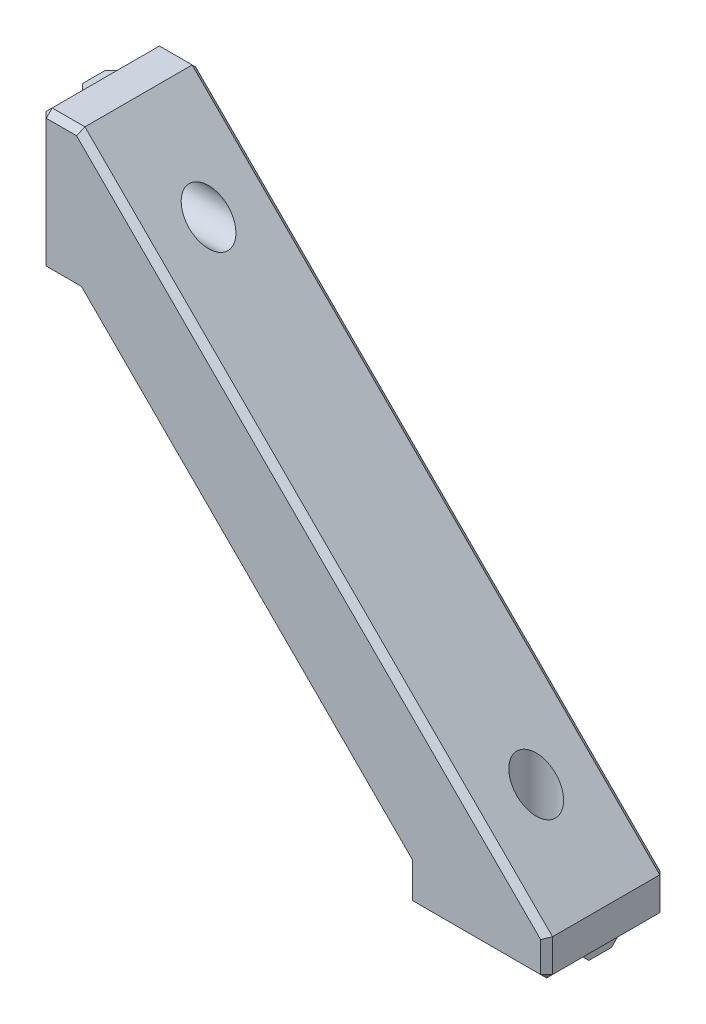
SolidWorks part; units mm, degrees
ref_plane "Front Plane" through (0, 0, 0) normal (0, 0, 1) x (1, 0, 0)
ref_plane "Top Plane" through (0, 0, 0) normal (0, 1, 0) x (1, 0, 0)
ref_plane "Right Plane" through (0, 0, 0) normal (1, 0, 0) x (0, 0, -1)
sketch "Sketch2" plane through (0, 0, 0) normal (0, 0, 1) x (1, 0, 0)
  line L0 (-8.1595, 72.9162) -> (70.3405, -5.5838)
  line L1 (70.3405, -5.5838) -> (46.8405, -5.5838)
  line L2 (46.8405, -5.5838) -> (-8.1595, 49.4162)
  line L3 (-8.1595, 49.4162) -> (-8.1595, 72.9162)
  line L4 (46.8405, -5.5838) -> (-8.1595, -5.5838) construction
  line L5 (-8.1595, -5.5838) -> (-8.1595, 49.4162) construction
  dimension "D1" = 23.5
  dimension "D2" = 55
extrude "Boss-Extrude1" add sketch "Sketch2" along normal mid plane 20
sketch "Sketch29" plane through (-8.1595, 0, 0) normal (-1, 0, 0) x (0, 0, 1)
  line L4 (-10, 72.9162) -> (-10, 49.4162)
  line L5 (-10, 49.4162) -> (10, 49.4162)
  line L6 (10, 49.4162) -> (10, 72.9162)
  line L7 (10, 72.9162) -> (-10, 72.9162)
  line L8 (-10, 72.9162) -> (-10, 49.4162)
  line L9 (-10, 49.4162) -> (10, 49.4162)
  line L10 (10, 49.4162) -> (10, 72.9162)
  line L11 (10, 72.9162) -> (-10, 72.9162)
  dimension "D1" = 0
extrude "Boss-Extrude4" add sketch "Sketch29" along normal blind 6.5
sketch "Sketch30" plane through (0, -5.5838, 0) normal (0, -1, 0) x (1, 0, 0)
  line L4 (46.8405, -10) -> (70.3405, -10)
  line L5 (70.3405, -10) -> (70.3405, 10)
  line L6 (70.3405, 10) -> (46.8405, 10)
  line L7 (46.8405, 10) -> (46.8405, -10)
  line L8 (46.8405, -10) -> (70.3405, -10)
  line L9 (70.3405, -10) -> (70.3405, 10)
  line L10 (70.3405, 10) -> (46.8405, 10)
  line L11 (46.8405, 10) -> (46.8405, -10)
  dimension "D1" = 0
extrude "Boss-Extrude5" add sketch "Sketch30" along normal blind 6.5
chamfer "Chamfer1" distance 1 angle 45 20 edges at (31.0905, 33.6662, -10) (19.3405, 21.9162, -10) (19.3405, 21.9162, 10) (31.0905, 33.6662, 10) (70.3405, -8.8338, 10) (58.5905, -12.0838, 10) (46.8405, -8.8338, 10) (-11.4095, 49.4162, 10) (-14.6595, 61.1662, 10) (-11.4095, 72.9162, 10) (46.8405, -8.8338, -10) (-11.4095, 49.4162, -10) (-14.6595, 49.4162, 0) (-14.6595, 61.1662, -10) (-14.6595, 72.9162, 0) (-11.4095, 72.9162, -10) (70.3405, -8.8338, -10) (70.3405, -12.0838, 0) (58.5905, -12.0838, -10) (46.8405, -12.0838, 0)
sketch "Sketch4" plane through (0, -12.0838, 0) normal (0, -1, 0) x (1, 0, 0)
  line L1 (47.8405, -2.9) -> (69.3405, -2.9)
  line L2 (47.8405, -2.9) -> (47.8405, 2.9)
  line L3 (47.8405, 2.9) -> (69.3405, 2.9)
  line L4 (69.3405, -2.9) -> (69.3405, 2.9)
  line L5 (47.8405, -2.9) -> (69.3405, 2.9) construction
  line L6 (47.8405, 2.9) -> (69.3405, -2.9) construction
  line L9 (69.3405, -9) -> (69.3405, 9) construction
  line L10 (47.8405, 9) -> (47.8405, -9) construction
  line L11 (69.3405, -9) -> (69.3405, 9)
  line L12 (47.8405, 9) -> (47.8405, -9)
  point P0 (58.5905, 0)
  line M12 (69.3405, -9) -> (69.3405, 9)
  line M14 (47.8405, 9) -> (47.8405, -9)
  dimension "D1" = 5.8
extrude "Boss-Extrude2" add sketch "Sketch4" along normal blind 1 contours L3 L1 M14 M12 region at (58.5905, -12.0838, 0)
sketch "Sketch5" plane through (-14.6595, 0, 0) normal (-1, 0, 0) x (0, 0, 1)
  line L1 (2.9, 50.4162) -> (-2.9, 50.4162)
  line L2 (2.9, 50.4162) -> (2.9, 71.9162)
  line L3 (2.9, 71.9162) -> (-2.9, 71.9162)
  line L4 (-2.9, 50.4162) -> (-2.9, 71.9162)
  line L5 (2.9, 50.4162) -> (-2.9, 71.9162) construction
  line L6 (2.9, 71.9162) -> (-2.9, 50.4162) construction
  line L7 (9, 71.9162) -> (-9, 71.9162) construction
  line L11 (-9, 50.4162) -> (9, 50.4162) construction
  point P0 (0, 61.1662)
  point P5 (0, 34.4162)
  point P9 (0, 0)
  dimension "D1" = 5.8
extrude "Boss-Extrude3" add sketch "Sketch5" along normal blind 1
chamfer "Chamfer2" distance 1 angle 45 4 edges at (-15.6595, 61.1662, 2.9) (-15.6595, 61.1662, -2.9) (58.5905, -13.0838, -2.9) (58.5905, -13.0838, 2.9)
ref_plane "Plane1" through (0, 27.9162, 0) normal (0, -1, 0) x (-1, 0, 0)
ref_plane "Plane2" through (25.3405, 0, 0) normal (-1, 0, 0) x (0, 0, 1)
sketch "Sketch31" plane through (25.3405, 0, 0) normal (-1, 0, 0) x (0, 0, 1)
  line L4 (-1.9, 50.4162) -> (1.9, 50.4162)
  line L5 (1.9, 50.4162) -> (1.9, 71.9162)
  line L6 (1.9, 71.9162) -> (-1.9, 71.9162)
  line L7 (-1.9, 71.9162) -> (-1.9, 50.4162)
  line L8 (-1.9, 50.4162) -> (1.9, 50.4162)
  line L9 (1.9, 50.4162) -> (1.9, 71.9162)
  line L10 (1.9, 71.9162) -> (-1.9, 71.9162)
  line L11 (-1.9, 71.9162) -> (-1.9, 50.4162)
  point P2 (0, 61.1662)
  point P4 (0, 61.1662)
  dimension "D1" = 0
sketch "Sketch32" plane through (0, 27.9162, 0) normal (0, -1, 0) x (-1, 0, 0)
  line L4 (-47.8405, -1.9) -> (-47.8405, 1.9)
  line L5 (-47.8405, 1.9) -> (-69.3405, 1.9)
  line L6 (-69.3405, 1.9) -> (-69.3405, -1.9)
  line L7 (-69.3405, -1.9) -> (-47.8405, -1.9)
  line L8 (-47.8405, -1.9) -> (-47.8405, 1.9)
  line L9 (-47.8405, 1.9) -> (-69.3405, 1.9)
  line L10 (-69.3405, 1.9) -> (-69.3405, -1.9)
  line L11 (-69.3405, -1.9) -> (-47.8405, -1.9)
  point P2 (-58.5905, 0)
  point P4 (-58.5905, 0)
  dimension "D1" = 0
hole_wizard "CBORE for M3 Hex Socket Head Cap Screw4" positions "Sketch33" profile "Sketch34" counterbore size "M3" standard "ISO" end condition through all
sketch "Sketch33" plane through (25.3405, 0, 0) normal (-1, 0, 0) x (0, 0, 1)
  point P0 (0, 61.1662)
sketch "Sketch34" plane through (25.3405, 61.1662, 0) normal (0, 1, 0) x (0, 0, -1)
  line L0 (0, 0) -> (0, 41)
  line L1 (0, 41) -> (1.7, 41)
  line L3 (1.7, 37.425) -> (1.725, 37.4)
  line L4 (1.725, 37.4) -> (3.25, 37.4)
  line L5 (3.25, 37.4) -> (3.25, 0.025)
  line L6 (3.25, 0.025) -> (3.275, 0)
  line L7 (3.275, 0) -> (0, 0)
  line L8 (-3.25, 0.025) -> (-3.275, 0) construction
  line L9 (-1.7, 37.425) -> (-1.725, 37.4) construction
  line L10 (1.7, 41) -> (1.7, 37.425)
  line L11 (0, -6.35) -> (0, 107.95) construction
  dimension "Thru Hole Dia." = 3.4
  dimension "Thru Hole Depth" = 41
  dimension "C'Bore Dia." = 6.5
  dimension "C'Bore Depth" = 37.4
  dimension "Near C'Sink Dia." = 6.55
  dimension "Near C'Sink Angle" = 90
  dimension "Mid C'Sink Dia." = 3.45
  dimension "Mid C'Sink Angle" = 90
hole_wizard "CBORE for M3 Hex Socket Head Cap Screw5" positions "Sketch35" profile "Sketch36" counterbore size "M3" standard "ISO" end condition through all
sketch "Sketch35" plane through (0, 27.9162, 0) normal (0, -1, 0) x (-1, 0, 0)
  point P0 (-58.5905, 0)
sketch "Sketch36" plane through (58.5905, 27.9162, 0) normal (1, 0, 0) x (0, 0, 1)
  line L0 (0, 0) -> (0, 41)
  line L1 (0, 41) -> (1.7, 41)
  line L3 (1.7, 37.425) -> (1.725, 37.4)
  line L4 (1.725, 37.4) -> (3.25, 37.4)
  line L5 (3.25, 37.4) -> (3.25, 0.025)
  line L6 (3.25, 0.025) -> (3.275, 0)
  line L7 (3.275, 0) -> (0, 0)
  line L8 (-3.25, 0.025) -> (-3.275, 0) construction
  line L9 (-1.7, 37.425) -> (-1.725, 37.4) construction
  line L10 (1.7, 41) -> (1.7, 37.425)
  line L11 (0, -6.35) -> (0, 107.95) construction
  dimension "Thru Hole Dia." = 3.4
  dimension "Thru Hole Depth" = 41
  dimension "C'Bore Dia." = 6.5
  dimension "C'Bore Depth" = 37.4
  dimension "Near C'Sink Dia." = 6.55
  dimension "Near C'Sink Angle" = 90
  dimension "Mid C'Sink Dia." = 3.45
  dimension "Mid C'Sink Angle" = 90
